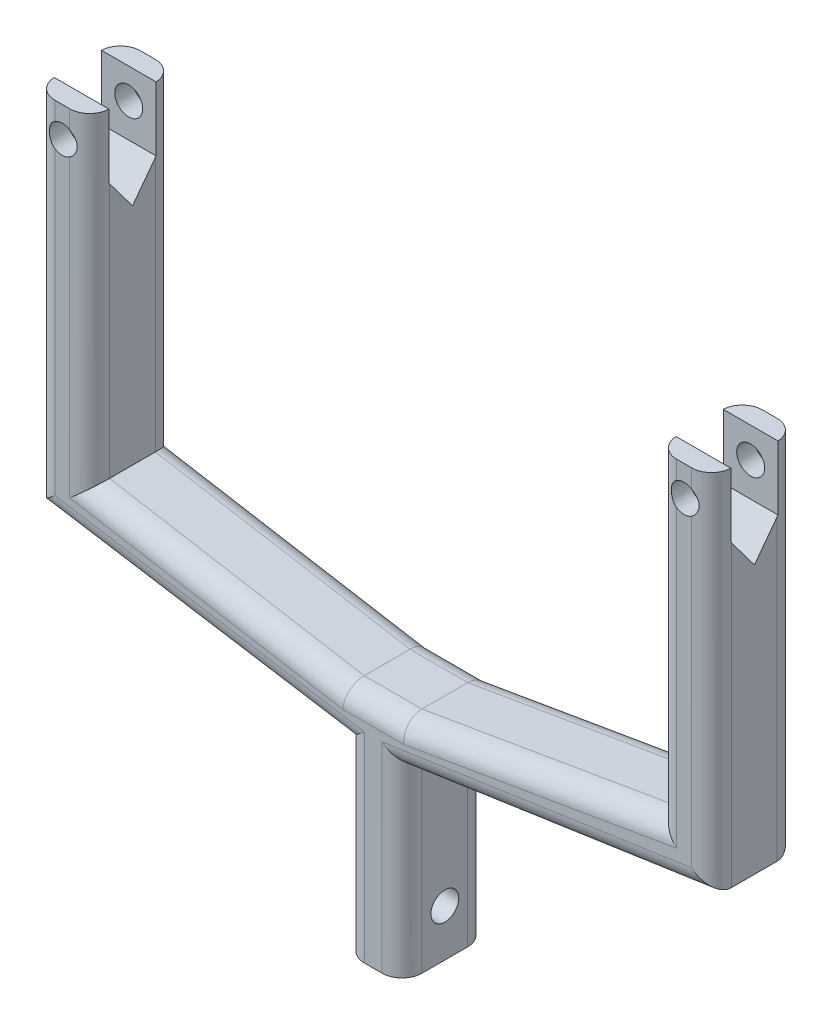
SolidWorks part; units mm, degrees
ref_plane "Front Plane" through (0, 0, 0) normal (0, 0, 1) x (1, 0, 0)
ref_plane "Top Plane" through (0, 0, 0) normal (0, 1, 0) x (1, 0, 0)
ref_plane "Right Plane" through (0, 0, 0) normal (1, 0, 0) x (0, 0, -1)
sketch "Sketch1" plane through (0, 0, 0) normal (0, 0, 1) x (1, 0, 0)
  line L0 (-688.0319, 825.9912) -> (-688.0319, 830.4224)
  line L1 (-720.5439, 846.0432) -> (-688.0319, 840.4939)
  line L2 (-727.5289, 886.9016) -> (-720.5439, 886.9016)
  line L3 (-720.5439, 886.9016) -> (-720.5439, 848.8016)
  line L4 (-727.5289, 886.9016) -> (-727.5289, 848.8016)
  line L6 (-727.5289, 848.8016) -> (-727.5289, 841.042)
  line L8 (-720.5439, 848.8016) -> (-720.5439, 846.0432)
  line L10 (-641.1689, 848.8016) -> (-641.1689, 840.4939)
  line L11 (-641.1689, 886.9016) -> (-641.1689, 848.8016)
  line L12 (-641.1689, 886.9016) -> (-648.1539, 886.9016)
  line L13 (-648.1539, 886.9016) -> (-648.1539, 848.8016)
  line L14 (-680.6659, 830.4224) -> (-680.6659, 825.9912)
  line L16 (-684.3489, 811.283) -> (-688.0319, 811.283)
  line L17 (-684.3489, 811.283) -> (-680.6659, 811.283)
  line L18 (-688.0319, 811.283) -> (-688.0319, 825.9912)
  line L19 (-680.6659, 811.283) -> (-680.6659, 825.9912)
  line L22 (-648.1539, 848.8016) -> (-648.1539, 846.0432)
  line L25 (-688.0319, 840.4939) -> (-680.6659, 840.4939)
  line L26 (-680.6659, 840.4939) -> (-648.1539, 846.0432)
  line L27 (-688.0319, 830.4224) -> (-688.0319, 834.6702)
  line L29 (-680.6659, 834.6702) -> (-680.6659, 830.4224)
  line L30 (-680.6659, 834.6702) -> (-641.1689, 840.4939)
  line L31 (-688.0319, 834.6702) -> (-727.5289, 841.042)
  dimension "D1" = 6.985
  dimension "D2" = 38.1
  dimension "D3" = 38.1
  dimension "D4" = 72.39
  dimension "D5" = 3.683
  dimension "D6" = 3.683
extrude "Boss-Extrude1" add sketch "Sketch1" along normal blind 10.922 contours L18 L0 L27 L31 L6 L4 L2 L3 L8 L1 L25 L26 L22 L13 L12 L11 L10 L30 L29 L14 L19 L17 L16
ref_plane "Plane1" through (-727.5289, 0, 0) normal (-1, 0, 0) x (0, 0, 1)
sketch "Sketch3" plane through (-727.5289, 0, 0) normal (-1, 0, 0) x (0, 0, 1)
  line L0 (0, 886.9016) -> (2.438, 886.9016)
  line L1 (10.922, 886.9016) -> (0, 886.9016) construction
  line B0 (2.438, 886.9016) -> (2.438, 878.7171)
  line B1 (8.4527, 886.9016) -> (8.4527, 878.7171)
  line B2 (2.438, 886.9016) -> (8.4527, 886.9016)
  line B3 (2.438, 878.7171) -> (5.4454, 874.7063)
  line B4 (5.4454, 874.7063) -> (8.4527, 878.7171)
sketch_block_instance "Block1-1"
sketch_block "Block1"
extrude "Cut-Extrude1" cut sketch "Sketch3" against normal blind 137.922 contours B3 B4 B1 B2 B0 region at (-727.5289, 881.7409, 5.4454)
ref_plane "Plane2" through (0, 0, 0) normal (0, 0, -1) x (-1, 0, 0)
sketch "Sketch4" plane through (0, 0, 0) normal (0, 0, -1) x (-1, 0, 0)
  circle A0 centre (724.0364, 883.056) radius 1.778
  dimension "D1" = 3.556
extrude "Cut-Extrude2" cut sketch "Sketch4" against normal blind 137.922
sketch "Sketch5" plane through (0, 0, 0) normal (0, 0, -1) x (-1, 0, 0)
  circle A0 centre (644.6614, 883.0463) radius 1.778
  dimension "D1" = 3.556
extrude "Cut-Extrude3" cut sketch "Sketch5" against normal blind 137.922
ref_plane "Plane3" through (-688.0319, 0, 0) normal (-1, 0, 0) x (0, 0, 1)
sketch "Sketch6" plane through (-688.0319, 0, 0) normal (-1, 0, 0) x (0, 0, 1)
  line L0 (5.461, 811.283) -> (5.461, 817.2599)
  line L1 (10.922, 811.283) -> (0, 811.283) construction
  circle A0 centre (5.461, 817.2599) radius 1.778
  dimension "D1" = 3.556
extrude "Cut-Extrude4" cut sketch "Sketch6" against normal blind 137.922 contours A0 region at (-688.0319, 816.0382, 6.6827)
fillet "Fillet1" radius 2.54 10 edges at (-680.6659, 822.9766, 10.922) (-688.0319, 822.9766, 10.922) (-707.7804, 837.8561, 10.922) (-704.2879, 843.2686, 10.922) (-664.4099, 843.2686, 10.922) (-660.9174, 837.5821, 10.922) (-641.1689, 863.6978, 10.922) (-648.1539, 866.4724, 10.922) (-727.5289, 863.9718, 10.922) (-720.5439, 866.4724, 10.922)
fillet "Fillet2" radius 2.54 10 edges at (-727.5289, 863.9718, 0) (-720.5439, 866.4724, 0) (-688.0319, 822.9766, 0) (-680.6659, 822.9766, 0) (-707.7804, 837.8561, 0) (-704.2879, 843.2686, 0) (-660.9174, 837.5821, 0) (-664.4099, 843.2686, 0) (-648.1539, 866.4724, 0) (-641.1689, 863.6978, 0)
fillet "Fillet3" radius 2.54 2 edges at (-684.3489, 840.4939, 0) (-684.3489, 840.4939, 10.922)
